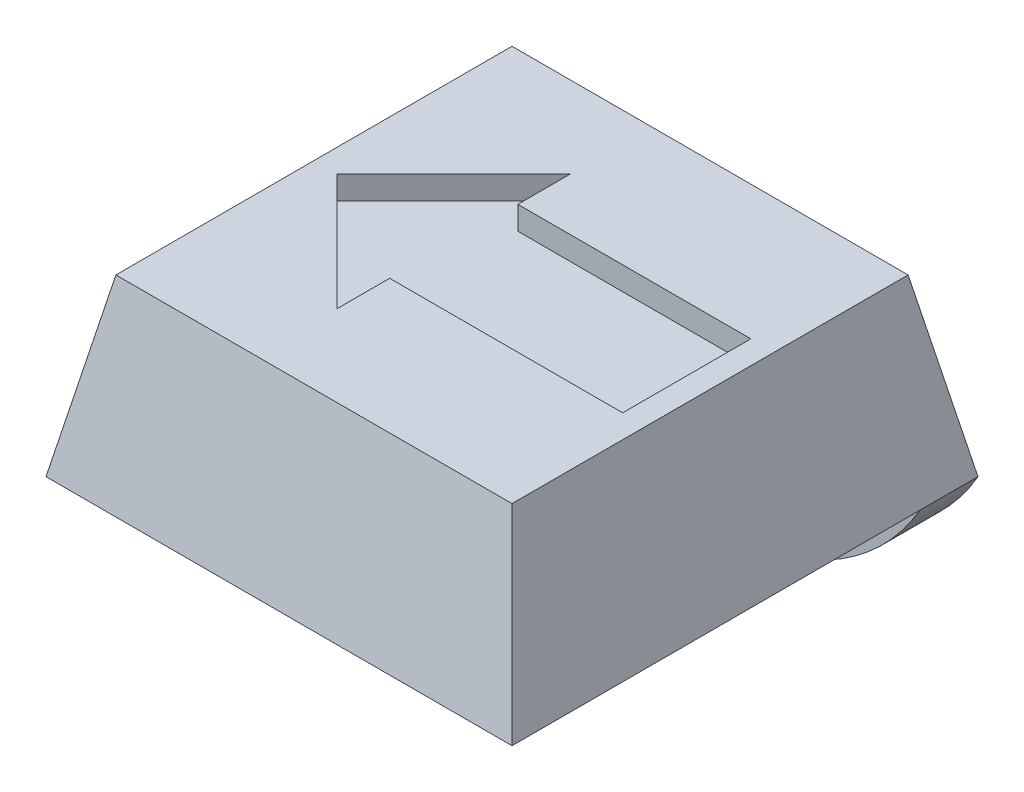
SolidWorks part; units mm, degrees
ref_plane "Front Plane" through (0, 0, 0) normal (0, 0, 1) x (1, 0, 0)
ref_plane "Top Plane" through (0, 0, 0) normal (0, 1, 0) x (1, 0, 0)
ref_plane "Right Plane" through (0, 0, 0) normal (1, 0, 0) x (0, 0, -1)
sketch "Sketch1" plane through (0, 0, 0) normal (0, 1, 0) x (1, 0, 0)
  line L1 (0, 0) -> (8, 0)
  line L2 (0, 0) -> (0, 8)
  line L3 (0, 8) -> (8, 8)
  line L4 (8, 0) -> (8, 8)
  dimension "D1" = 8
  dimension "D2" = 8
extrude "Boss-Extrude1" add sketch "Sketch1" along normal blind 3
sketch "Sketch2" plane through (0, 0, 0) normal (0, 0, 1) x (1, 0, 0)
  line L0 (0, 0) -> (0.6, 3)
  line L1 (0, 3) -> (8, 3) construction
  line L2 (0.6, 3) -> (0, 3)
  line L3 (0, 3) -> (0, 0)
  line L4 (8, 0) -> (7.4, 3)
  line L5 (7.4, 3) -> (8, 3)
  line L6 (8, 3) -> (8, 0)
  dimension "D1" = 0.6
  dimension "D2" = 0.6
extrude "Cut-Extrude1" cut sketch "Sketch2" against normal through all both and the other way through all
sketch "Sketch3" plane through (0, 0, 0) normal (1, 0, 0) x (0, 0, -1)
  line L0 (0, 0) -> (0.6, 3)
  line L1 (8, 3) -> (0, 3) construction
  line L2 (0.6, 3) -> (0, 3)
  line L3 (0, 3) -> (0, 0)
  line L4 (8, 3) -> (7.4, 3)
  line L5 (7.4, 3) -> (8, 0)
  line L6 (8, 3) -> (8, 0)
  dimension "D1" = 0.6
  dimension "D2" = 0.6
extrude "Cut-Extrude2" cut sketch "Sketch3" along normal blind 11
sketch "Sketch4" plane through (0, 0, 0) normal (0, -1, 0) x (1, 0, 0)
  line L0 (8, 0) -> (8, -8) construction
  line L3 (0, 0) -> (8, 0) construction
  circle A0 centre (4, -3.75) radius 1.8
  dimension "D1" = 3.6
  dimension "D2" = 4
  dimension "D3" = 3.75
extrude "Cut-Extrude3" cut sketch "Sketch4" against normal blind 0.8
sketch "Sketch5" plane through (0, 0, 0) normal (0, -1, 0) x (1, 0, 0)
  line L0 (8, 0) -> (8, -8) construction
  line L1 (0, -8) -> (8, -8)
  line L2 (0, -8) -> (0, -7)
  line L3 (0, -7) -> (8, -7)
  line L4 (8, -8) -> (8, -7)
  dimension "D1" = 1
extrude "Boss-Extrude2" add sketch "Sketch5" along normal blind 2
fillet "Fillet1" radius 4 2 edges at (8, -2, -7.5) (0, -2, -7.5)
sketch "Sketch6" plane through (0, 3, 0) normal (0, 1, 0) x (1, 0, 0)
  line L0 (3, 5.1) -> (3, 6)
  line L5 (3, 5.1) -> (7, 5.1)
  line L6 (3, 5.1) -> (3, 2.9)
  line L7 (3, 2.9) -> (7, 2.9)
  line L12 (7, 5.1) -> (7, 2.9)
  line L13 (3, 6) -> (1, 4)
  line L14 (1, 4) -> (3, 2)
  line L15 (3, 2) -> (3, 2.9)
  line L16 (7.4, 7.4) -> (0.6, 7.4) construction
  line L17 (7.4, 0.6) -> (0.6, 0.6) construction
  line L18 (7.4, 7.4) -> (7.4, 0.6) construction
  line L19 (0.6, 7.4) -> (0.6, 0.6) construction
  point P15 (0.6, 4)
  dimension "D1" = 4
  dimension "D2" = 1.4
  dimension "D3" = 1.4
  dimension "D4" = 0.4
  dimension "D5" = 0.4
  dimension "D6" = 2.3
  dimension "D7" = 2.3
  dimension "D8" = 0
extrude "Cut-Extrude4" cut sketch "Sketch6" against normal blind 0.4 contours L14 L15 L6 L0 L13 | L12 L5 L6 L7 region at (2.3333, 3, -4) region at (5, 3, -4)
